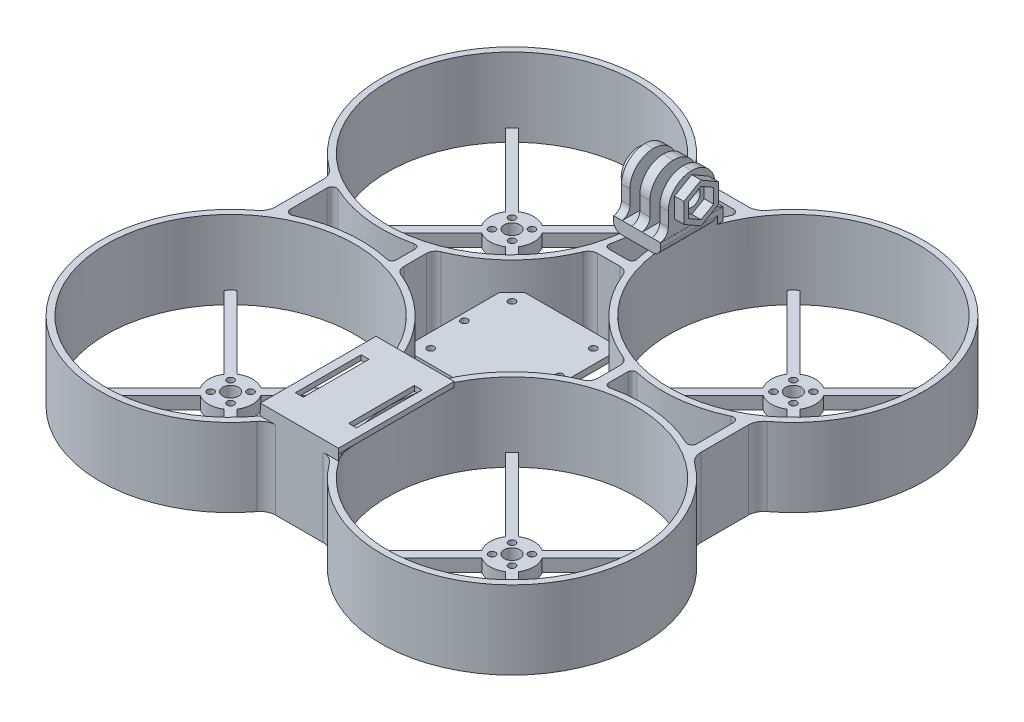
SolidWorks part; units mm, degrees
ref_plane "Front Plane" through (0, 0, 0) normal (0, 0, 1) x (1, 0, 0)
ref_plane "Top Plane" through (0, 0, 0) normal (0, 1, 0) x (1, 0, 0)
ref_plane "Right Plane" through (0, 0, 0) normal (1, 0, 0) x (0, 0, -1)
ref_axis "X Axis" through (-102.512, 0, 0) along (1, 0, 0)
ref_axis "Y Axis" through (0, 0, -107.1526) along (0, 0, 1)
ref_axis "Z Axis" through (0, 27.7441, 0) along (0, -1, 0)
ref_plane "Prop Guards Plane" through (0, 15, 0) normal (0, 1, 0) x (1, 0, 0)
ref_plane "Motor mount plane" through (0, 0, 0) normal (0, 1, 0) x (1, 0, 0)
sketch "Sketch1" plane through (0, 0, 0) normal (0, 1, 0) x (1, 0, 0)
  line L2 (-41.818, 48.182) -> (-48.182, 41.818) construction
  line L21 (-48.1744, 48.1895) -> (-41.8105, 41.8256) construction
  line L22 (48.182, 48.182) -> (41.818, 41.818) construction
  line L38 (-45, -45) -> (-45, 45) construction
  line L39 (-45, 45) -> (-40.5, 45) construction
  line L40 (45, -45) -> (45, 45) construction
  line L41 (-45, -45) -> (45, 45) construction
  line L42 (-45, 45) -> (45, -45) construction
  line L43 (-45, 45) -> (45, 45) construction
  line L44 (41.818, 48.182) -> (48.182, 41.818) construction
  line L45 (45, 45) -> (49.5, 45) construction
  line L46 (41.818, -41.818) -> (48.182, -48.182) construction
  line L47 (41.818, -48.182) -> (48.182, -41.818) construction
  line L48 (-45, -45) -> (45, -45) construction
  line L49 (-41.818, -41.818) -> (-48.182, -48.182) construction
  line L50 (-48.182, -41.818) -> (-41.818, -48.182) construction
  line L59 (0, 107.1526) -> (0, -108.5266) construction
  circle A2 centre (-45, 45) radius 4.5 construction
  circle A3 centre (-48.1744, 48.1895) radius 1.1
  circle A4 centre (-41.818, 48.182) radius 1.1
  circle A5 centre (-41.8105, 41.8256) radius 1.1
  circle A6 centre (-48.182, 41.818) radius 1.1
  circle A22 centre (-45, 45) radius 2.5
  circle A33 centre (-45, 45) radius 7
  circle A34 centre (-45, 45) radius 38.25 construction
  circle A35 centre (45, 45) radius 4.5 construction
  circle A36 centre (41.818, 48.182) radius 1.1
  circle A37 centre (48.182, 48.182) radius 1.1
  circle A38 centre (48.182, 41.818) radius 1.1
  circle A39 centre (41.818, 41.818) radius 1.1
  circle A40 centre (45, 45) radius 2.5
  circle A41 centre (45, 45) radius 7
  circle A42 centre (45, -45) radius 4.5 construction
  circle A43 centre (41.818, -48.182) radius 1.1
  circle A44 centre (41.818, -41.818) radius 1.1
  circle A45 centre (48.182, -41.818) radius 1.1
  circle A46 centre (48.182, -48.182) radius 1.1
  circle A47 centre (45, -45) radius 2.5
  circle A48 centre (45, -45) radius 7
  circle A49 centre (-45, -45) radius 4.5 construction
  circle A50 centre (-48.182, -41.818) radius 1.1
  circle A51 centre (-41.818, -41.818) radius 1.1
  circle A52 centre (-41.818, -48.182) radius 1.1
  circle A53 centre (-48.182, -48.182) radius 1.1
  circle A54 centre (-45, -45) radius 2.5
  circle A55 centre (-45, -45) radius 7
  circle A56 centre (45, 45) radius 38.25 construction
  circle A57 centre (45, -45) radius 38.25 construction
  circle A58 centre (-45, -45) radius 38.25 construction
  point P8 (45, 45)
  point P9 (0, 0)
  point P16 (-45, 45)
  point P26 (0, 0)
  point P29 (45, 45)
  point P39 (45, -45)
  point P46 (45, -45)
  point P50 (-45, 45)
  point P55 (-45, -45)
  point P64 (-45, -45)
  point P67 (0, 0)
  point P76 (0, 0)
  point P85 (0, 0)
  point P104 (0, 0)
  point P120 (0, 0)
  dimension "D3" = 14
  dimension "D4" = 9
  dimension "D7" = 76.5
  dimension "D5" = 2.2
  dimension "D6" = 5
  dimension "D8" = 9
  dimension "D10" = 5
  dimension "D12" = 14
  dimension "D13" = 9
  dimension "D15" = 5
  dimension "D17" = 9
  dimension "D19" = 5
  dimension "D20" = 14
  dimension "D11" = 90
extrude "Boss-Extrude3" add sketch "Sketch1" along normal blind 4
sketch "Sketch10" plane through (0, 0, 0) normal (0, 1, 0) x (1, 0, 0)
  line L0 (-72, 0) -> (0, 0) construction
  line L16 (0, 0) -> (0, 72) construction
  circle A0 centre (-45, 45) radius 39.75
  circle A1 centre (45, 45) radius 39.75
  circle A2 centre (45, -45) radius 39.75
  circle A3 centre (-45, -45) radius 39.75
  circle A4 centre (-45, 45) radius 41.75
  circle A5 centre (45, 45) radius 41.75
  circle A6 centre (45, -45) radius 41.75
  circle A7 centre (-45, -45) radius 41.75
  point P46 (0, 0)
  dimension "D1" = 79.5
  dimension "D3" = 72
  dimension "D2" = 2
extrude "Boss-Extrude8" add sketch "Sketch10" along normal blind 25 separate body contours A7 A3 | A6 A2 | A5 A1 | A4 A0 region at (-85.5691, 0, -45) region at (4.4309, 0, -45) region at (4.4309, 0, 45) region at (-85.5691, 0, 45)
sketch "Sketch21" plane through (0, 25, 0) normal (0, 1, 0) x (1, 0, 0)
  line L0 (-4.1275, 0) -> (4.1275, 0) construction
  line L1 (-34, 4.7252) -> (-34, -4.7252)
  line L6 (-31, 5.6673) -> (-31, -5.6673)
  line L7 (-34, 4.7252) -> (-31, 5.6673)
  line L8 (-31, -5.6673) -> (-34, -4.7252)
  line L33 (-68, 10.1566) -> (-68, -10.1566)
  line L45 (-65, 8.3522) -> (-65, -8.3522)
  line L46 (-68, 10.1566) -> (-65, 8.3522)
  line L47 (-68, -10.1566) -> (-65, -8.3522)
  line L65 (-10.1566, 68) -> (-8.3522, 65)
  line L66 (8.3522, 65) -> (-8.3522, 65)
  line L67 (10.1566, 68) -> (8.3522, 65)
  line L68 (10.1566, 68) -> (-10.1566, 68)
  line L69 (-5.6673, 31) -> (-4.7252, 34)
  line L70 (4.7252, 34) -> (-4.7252, 34)
  line L71 (4.7252, 34) -> (5.6673, 31)
  line L72 (5.6673, 31) -> (-5.6673, 31)
  line L73 (68, 10.1566) -> (65, 8.3522)
  line L74 (65, -8.3522) -> (65, 8.3522)
  line L75 (68, -10.1566) -> (65, -8.3522)
  line L76 (68, -10.1566) -> (68, 10.1566)
  line L77 (31, 5.6673) -> (34, 4.7252)
  line L78 (34, -4.7252) -> (34, 4.7252)
  line L79 (34, -4.7252) -> (31, -5.6673)
  line L80 (31, -5.6673) -> (31, 5.6673)
  line L81 (10.1566, -68) -> (8.3522, -65)
  line L82 (-8.3522, -65) -> (8.3522, -65)
  line L83 (-10.1566, -68) -> (-8.3522, -65)
  line L84 (-10.1566, -68) -> (10.1566, -68)
  line L85 (5.6673, -31) -> (4.7252, -34)
  line L86 (-4.7252, -34) -> (4.7252, -34)
  line L87 (-4.7252, -34) -> (-5.6673, -31)
  line L88 (-5.6673, -31) -> (5.6673, -31)
  circle A0 centre (-45, 45) radius 41.75 construction
  circle A1 centre (-45, -45) radius 41.75 construction
  point P0 (0, 0)
  point P38 (-0.0792, 0.1295)
  point P39 (0, 0)
  dimension "D1" = 3
  dimension "D2" = 3
  dimension "D3" = 68
  dimension "D4" = 34
  dimension "D5" = 4
extrude "Boss-Extrude15" add sketch "Sketch21" against normal up to surface (25 mm away) up to face at (-45, 0, -5.25)
sketch "Sketch22" plane through (0, 0, 0) normal (0, 1, 0) x (1, 0, 0)
  line L0 (0, 0) -> (-45, 45) construction
  line L2 (-39.1046, 41.2259) -> (-15.2428, 17.3641)
  line L3 (-39.1046, 41.2259) -> (-41.2259, 39.1046)
  line L4 (-41.2259, 39.1046) -> (-17.3641, 15.2428)
  line L5 (-15.2428, 17.3641) -> (-17.3641, 15.2428)
  line L6 (-39.1046, 41.2259) -> (-17.3641, 15.2428) construction
  line L7 (-41.2259, 39.1046) -> (-15.2428, 17.3641) construction
  line L8 (-48.7741, 39.1046) -> (-50.8954, 41.2259)
  line L9 (-48.7741, 39.1046) -> (-72.6359, 15.2428)
  line L10 (-72.6359, 15.2428) -> (-74.7572, 17.3641)
  line L11 (-50.8954, 41.2259) -> (-74.7572, 17.3641)
  line L12 (-50.8954, 48.7741) -> (-48.7741, 50.8954)
  line L13 (-50.8954, 48.7741) -> (-74.7572, 72.6359)
  line L14 (-74.7572, 72.6359) -> (-72.6359, 74.7572)
  line L15 (-48.7741, 50.8954) -> (-72.6359, 74.7572)
  line L16 (-41.2259, 50.8954) -> (-39.1046, 48.7741)
  line L17 (-41.2259, 50.8954) -> (-17.3641, 74.7572)
  line L18 (-17.3641, 74.7572) -> (-15.2428, 72.6359)
  line L19 (-39.1046, 48.7741) -> (-15.2428, 72.6359)
  line L20 (48.7741, 50.8954) -> (50.8954, 48.7741)
  line L21 (50.8954, 48.7741) -> (74.7572, 72.6359)
  line L22 (72.6359, 74.7572) -> (74.7572, 72.6359)
  line L23 (48.7741, 50.8954) -> (72.6359, 74.7572)
  line L24 (39.1046, 48.7741) -> (41.2259, 50.8954)
  line L25 (41.2259, 50.8954) -> (17.3641, 74.7572)
  line L26 (15.2428, 72.6359) -> (17.3641, 74.7572)
  line L27 (39.1046, 48.7741) -> (15.2428, 72.6359)
  line L28 (50.8954, 41.2259) -> (48.7741, 39.1046)
  line L29 (48.7741, 39.1046) -> (72.6359, 15.2428)
  line L30 (74.7572, 17.3641) -> (72.6359, 15.2428)
  line L31 (50.8954, 41.2259) -> (74.7572, 17.3641)
  line L32 (41.2259, 39.1046) -> (39.1046, 41.2259)
  line L33 (41.2259, 39.1046) -> (17.3641, 15.2428)
  line L34 (17.3641, 15.2428) -> (15.2428, 17.3641)
  line L35 (39.1046, 41.2259) -> (15.2428, 17.3641)
  line L36 (50.8954, -48.7741) -> (48.7741, -50.8954)
  line L37 (48.7741, -50.8954) -> (72.6359, -74.7572)
  line L38 (74.7572, -72.6359) -> (72.6359, -74.7572)
  line L39 (50.8954, -48.7741) -> (74.7572, -72.6359)
  line L40 (48.7741, -39.1046) -> (50.8954, -41.2259)
  line L41 (50.8954, -41.2259) -> (74.7572, -17.3641)
  line L42 (72.6359, -15.2428) -> (74.7572, -17.3641)
  line L43 (48.7741, -39.1046) -> (72.6359, -15.2428)
  line L44 (41.2259, -50.8954) -> (39.1046, -48.7741)
  line L45 (39.1046, -48.7741) -> (15.2428, -72.6359)
  line L46 (17.3641, -74.7572) -> (15.2428, -72.6359)
  line L47 (41.2259, -50.8954) -> (17.3641, -74.7572)
  line L48 (39.1046, -41.2259) -> (41.2259, -39.1046)
  line L49 (39.1046, -41.2259) -> (15.2428, -17.3641)
  line L50 (15.2428, -17.3641) -> (17.3641, -15.2428)
  line L51 (41.2259, -39.1046) -> (17.3641, -15.2428)
  line L52 (-48.7741, -50.8954) -> (-50.8954, -48.7741)
  line L53 (-50.8954, -48.7741) -> (-74.7572, -72.6359)
  line L54 (-72.6359, -74.7572) -> (-74.7572, -72.6359)
  line L55 (-48.7741, -50.8954) -> (-72.6359, -74.7572)
  line L56 (-39.1046, -48.7741) -> (-41.2259, -50.8954)
  line L57 (-41.2259, -50.8954) -> (-17.3641, -74.7572)
  line L58 (-15.2428, -72.6359) -> (-17.3641, -74.7572)
  line L59 (-39.1046, -48.7741) -> (-15.2428, -72.6359)
  line L60 (-50.8954, -41.2259) -> (-48.7741, -39.1046)
  line L61 (-48.7741, -39.1046) -> (-72.6359, -15.2428)
  line L62 (-74.7572, -17.3641) -> (-72.6359, -15.2428)
  line L63 (-50.8954, -41.2259) -> (-74.7572, -17.3641)
  line L64 (-41.2259, -39.1046) -> (-39.1046, -41.2259)
  line L65 (-41.2259, -39.1046) -> (-17.3641, -15.2428)
  line L66 (-17.3641, -15.2428) -> (-15.2428, -17.3641)
  line L67 (-39.1046, -41.2259) -> (-15.2428, -17.3641)
  circle A0 centre (-45, 45) radius 7 construction
  point P4 (-28.2343, 28.2343)
  point P9 (-27.94, 27.94)
  point P10 (-45, 45)
  point P30 (-45, 45)
  point P77 (-0.0652, 0)
  point P78 (0, 0)
  dimension "D1" = 3
  dimension "D2" = 4
  dimension "D3" = 4
extrude "Boss-Extrude16" add sketch "Sketch22" along normal blind 4
ref_plane "PCB Plane" through (0, 14, 0) normal (0, 1, 0) x (1, 0, 0)
sketch "Sketch13" plane through (0, 14, 0) normal (0, 1, 0) x (1, 0, 0)
  line L0 (-15.25, 0) -> (15.25, 0) construction
  line L1 (-13, -13) -> (13, -13) construction
  line L2 (-13, -13) -> (-13, 13) construction
  line L3 (-13, 13) -> (13, 13) construction
  line L4 (13, -13) -> (13, 13) construction
  line L5 (-13, -13) -> (13, 13) construction
  line L6 (-13, 13) -> (13, -13) construction
  line L7 (-14.5, -17.5) -> (14.5, -17.5)
  line L8 (-17.5, -14.5) -> (-17.5, 14.5)
  line L9 (-14.5, 17.5) -> (14.5, 17.5)
  line L10 (17.5, -14.5) -> (17.5, 14.5)
  line L11 (-17.5, -17.5) -> (17.5, 17.5) construction
  line L12 (-17.5, 17.5) -> (17.5, -17.5) construction
  circle A0 centre (-13, 13) radius 1.1
  circle A1 centre (13, 13) radius 1.1
  circle A2 centre (13, -13) radius 1.1
  circle A3 centre (-13, -13) radius 1.1
  circle A4 centre (-15.25, 0) radius 1.1
  circle A5 centre (15.25, 0) radius 1.1
  arc A6 (-14.5, -17.5) -> (-17.5, -14.5) centre (-14.5, -14.5) cw
  arc A7 (14.5, -17.5) -> (17.5, -14.5) centre (14.5, -14.5) ccw
  arc A8 (14.5, 17.5) -> (17.5, 14.5) centre (14.5, 14.5) cw
  arc A9 (-17.5, 14.5) -> (-14.5, 17.5) centre (-14.5, 14.5) cw
  point P0 (0, 0)
  point P10 (0, 0)
  point P17 (0, 0)
  dimension "D2" = 2.2
  dimension "D5" = 2.2
  dimension "D6" = 3
  dimension "D1" = 26
  dimension "D3" = 35
  dimension "D4" = 30.5
extrude "Boss-Extrude9" add sketch "Sketch13" along normal blind 2
sketch "Sketch14" plane through (0, 25, 0) normal (0, 1, 0) x (1, 0, 0)
  line L0 (0, 0) -> (0, 50) construction
  line L2 (-7.5, 40) -> (7.5, 40)
  line L3 (-7.5, 40) -> (-7.5, 60)
  line L4 (-7.5, 60) -> (7.5, 60)
  line L5 (7.5, 40) -> (7.5, 60)
  line L6 (-7.5, 40) -> (7.5, 60) construction
  line L7 (-7.5, 60) -> (7.5, 40) construction
  dimension "D1" = 20
  dimension "D2" = 15
  dimension "D3" = 50
extrude "Boss-Extrude10" add sketch "Sketch14" along normal blind 4
sketch "Sketch15" plane through (0, 29, 0) normal (0, 1, 0) x (1, 0, 0)
  line L0 (-7.5, 60) -> (7.5, 40) construction
  line L1 (-7.5, 40) -> (7.5, 60) construction
  line L2 (7.5, 40) -> (7.5, 60) construction
  line L3 (-7.5, 50) -> (7.5, 50) construction
  line L5 (0, -49.9102) -> (0, 49.9102) construction
  line L6 (-1.625, 42.5) -> (1.625, 42.5)
  line L7 (-1.625, 42.5) -> (-1.625, 57.5)
  line L8 (-1.625, 57.5) -> (1.625, 57.5)
  line L9 (1.625, 42.5) -> (1.625, 57.5)
  line L10 (-1.625, 42.5) -> (1.625, 57.5) construction
  line L11 (-1.625, 57.5) -> (1.625, 42.5) construction
  line L12 (-7.475, 42.5) -> (-4.775, 42.5)
  line L13 (-7.475, 42.5) -> (-7.475, 57.5)
  line L14 (-7.475, 57.5) -> (-4.775, 57.5)
  line L15 (-4.775, 42.5) -> (-4.775, 57.5)
  line L16 (-7.475, 42.5) -> (-4.775, 57.5) construction
  line L17 (-7.475, 57.5) -> (-4.775, 42.5) construction
  line L18 (7.475, 57.5) -> (4.775, 57.5)
  line L19 (4.775, 42.5) -> (4.775, 57.5)
  line L20 (7.475, 42.5) -> (4.775, 42.5)
  line L21 (7.475, 42.5) -> (7.475, 57.5)
  point P9 (0, 50)
  point P10 (0, 50)
  point P17 (0, 50)
  point P23 (-6.125, 50)
  dimension "D1" = 3.25
  dimension "D2" = 15
  dimension "D3" = 15
  dimension "D4" = 2.7
  dimension "D5" = 3.15
extrude "Boss-Extrude11" add sketch "Sketch15" along normal blind 15
fillet "Fillet10" radius 7.5 6 edges at (6.125, 44, -42.5) (6.125, 44, -57.5) (0, 44, -42.5) (0, 44, -57.5) (-6.125, 44, -42.5) (-6.125, 44, -57.5)
sketch "Sketch16" plane through (-7.475, 0, 0) normal (-1, 0, 0) x (0, 0, 1)
  circle A0 centre (-50, 36.5) radius 7.5 construction
  circle A3 centre (-50, 36.5) radius 2.7
  arc A4 (-50, 44) -> (-57.5, 36.5) centre (-50, 36.5) ccw construction
  dimension "D1" = 5.4
extrude "Cut-Extrude1" cut sketch "Sketch16" against normal blind 17 and the other way blind 12
sketch "Sketch17" plane through (-7.475, 0, 0) normal (-1, 0, 0) x (0, 0, 1)
  circle A0 centre (-50, 36.5) radius 5.5
  circle A1 centre (-50, 36.5) radius 2.7
  dimension "D1" = 11
extrude "Boss-Extrude12" add sketch "Sketch17" along normal blind 2.1
sketch "Sketch23" plane through (7.475, 0, 0) normal (1, 0, 0) x (0, 0, -1)
  line L0 (50, 42.8509) -> (44.5, 39.6754)
  line L1 (50, 41.1188) -> (46, 38.8094)
  line L2 (46, 38.8094) -> (46, 34.1906)
  line L3 (46, 34.1906) -> (50, 31.8812)
  line L4 (50, 31.8812) -> (54, 34.1906)
  line L5 (54, 34.1906) -> (54, 38.8094)
  line L6 (54, 38.8094) -> (50, 41.1188)
  line L7 (44.5, 39.6754) -> (44.5, 33.3246)
  line L8 (44.5, 33.3246) -> (50, 30.1491)
  line L9 (50, 30.1491) -> (55.5, 33.3246)
  line L10 (55.5, 33.3246) -> (55.5, 39.6754)
  line L11 (55.5, 39.6754) -> (50, 42.8509)
  circle A0 centre (50, 36.5) radius 4 construction
  dimension "D1" = 8
  dimension "D2" = 1.5
extrude "Boss-Extrude17" add sketch "Sketch23" along normal blind 3
fillet "Fillet12" radius 2.5 2 edges at (-7.5, 25, -49.0919) (7.5, 25, -49.0919)
fillet "Fillet11" radius 3 6 edges at (6.125, 29, -42.5) (0, 29, -42.5) (-6.125, 29, -42.5) (0, 29, -57.5) (6.125, 29, -57.5) (-6.125, 29, -57.5)
ref_plane "Battery plane" through (0, 27, 0) normal (0, 1, 0) x (1, 0, 0)
sketch "Sketch24" plane through (0, 27, 0) normal (0, 1, 0) x (1, 0, 0)
  line L0 (0, 0) -> (0, -49) construction
  line L1 (-8.5, -49) -> (8.5, -49) construction
  line L6 (5.6673, -31) -> (-5.6673, -31) construction
  line L7 (-12.5, -31) -> (12.5, -31)
  line L8 (-12.5, -31) -> (-12.5, -68)
  line L9 (-9.75, -59.5) -> (-7.25, -59.5)
  line L10 (-9.75, -59.5) -> (-9.75, -38.5)
  line L11 (-9.75, -38.5) -> (-7.25, -38.5)
  line L12 (-7.25, -59.5) -> (-7.25, -38.5)
  line L13 (-9.75, -59.5) -> (-7.25, -38.5) construction
  line L14 (-9.75, -38.5) -> (-7.25, -59.5) construction
  line L15 (7.25, -59.5) -> (9.75, -59.5)
  line L16 (7.25, -59.5) -> (7.25, -38.5)
  line L17 (7.25, -38.5) -> (9.75, -38.5)
  line L18 (9.75, -59.5) -> (9.75, -38.5)
  line L19 (7.25, -59.5) -> (9.75, -38.5) construction
  line L20 (7.25, -38.5) -> (9.75, -59.5) construction
  line L21 (-12.5, -68) -> (12.5, -68)
  line L22 (12.5, -31) -> (12.5, -68)
  line L23 (-12.5, -31) -> (12.5, -68) construction
  line L24 (-12.5, -68) -> (12.5, -31) construction
  line L25 (-10.1566, -68) -> (10.1566, -68) construction
  point P4 (0, -49.5)
  point P9 (-8.5, -49)
  point P14 (8.5, -49)
  point P19 (0, -49)
  dimension "D2" = 25
  dimension "D3" = 49
  dimension "D4" = 17
  dimension "D5" = 21
  dimension "D6" = 2.5
extrude "Boss-Extrude18" add sketch "Sketch24" along normal blind 1.6 separate body
sketch "Sketch25" plane through (0, 25, 0) normal (0, 1, 0) x (1, 0, 0)
  line L0 (-7.797, -31) -> (7.797, -31)
  line L1 (5.6673, -31) -> (-5.6673, -31) construction
  line L2 (-6.8023, -34) -> (6.8023, -34)
  line L3 (-4.7252, -34) -> (4.7252, -34) construction
  circle A0 centre (-45, -45) radius 39.75 construction
  circle A1 centre (45, -45) radius 39.75 construction
  arc A2 (-7.797, -31) -> (-6.8023, -34) centre (-45, -45) cw
  arc A3 (7.797, -31) -> (6.8023, -34) centre (45, -45) ccw
sketch "Sketch26" plane through (0, 27, 0) normal (0, -1, 0) x (1, 0, 0)
  line L0 (12.5, 68) -> (12.5, 31) construction
  line L1 (-12.5, 31) -> (12.5, 31)
  line L2 (-12.5, 31) -> (-12.5, 36.195)
  line L3 (-12.5, 36.195) -> (12.5, 36.195)
  line L4 (12.5, 31) -> (12.5, 36.195)
loft "Loft1" add profiles "Sketch25", "Sketch26"
sketch "Sketch27" plane through (0, 25, 0) normal (0, 1, 0) x (1, 0, 0)
  line L0 (-12.5799, -68) -> (12.5799, -68)
  line L2 (-10.1566, -68) -> (10.1566, -68) construction
  line L3 (10.648, -65) -> (-10.648, -65)
  line L4 (8.3522, -65) -> (-8.3522, -65) construction
  arc A0 (-7.797, -31) -> (-6.8023, -34) centre (-45, -45) ccw construction
  arc A1 (6.8023, -34) -> (7.797, -31) centre (45, -45) ccw construction
  arc A2 (-10.648, -65) -> (-12.5799, -68) centre (-45, -45) cw
  arc A3 (10.648, -65) -> (12.5799, -68) centre (45, -45) ccw
  point P17 (0, 0)
sketch "Sketch28" plane through (0, 27, 0) normal (0, -1, 0) x (1, 0, 0)
  line L0 (-12.5, 36.195) -> (-12.5, 68) construction
  line L1 (12.5, 68) -> (-12.5, 68)
  line L2 (12.5, 68) -> (12.5, 63.3482)
  line L3 (12.5, 63.3482) -> (-12.5, 63.3482)
  line L4 (-12.5, 68) -> (-12.5, 63.3482)
loft "Loft2" add profiles "Sketch27", "Sketch28"
fillet "Fillet14" radius 5 8 edges at (-68, 12.5, 10.1566) (-68, 12.5, -10.1566) (10.1566, 12.5, -68) (-10.1566, 12.5, -68) (68, 12.5, 10.1566) (68, 12.5, -10.1566)
fillet "Fillet15" radius 1.5 8 edges at (65, 12.5, -8.3522) (65, 12.5, 8.3522) (8.3522, 12.5, -65) (-8.3522, 12.5, -65) (-65, 12.5, -8.3522) (-65, 12.5, 8.3522)
fillet "Fillet16" radius 3 8 edges at (-31, 12.5, -5.6673) (-31, 12.5, 5.6673) (-5.6673, 12.5, -31) (5.6673, 12.5, -31) (31, 12.5, -5.6673) (31, 12.5, 5.6673)
fillet "Fillet17" radius 1.3 8 edges at (34, 12.5, -4.7252) (34, 12.5, 4.7252) (4.7252, 12.5, -34) (-4.7252, 12.5, -34) (-34, 12.5, -4.7252) (-34, 12.5, 4.7252)
equation "\"Prop Dia\"= 76.2mm"
equation "\"ground_clearance\"= 15mm"
equation "\"D1@Prop Guards Plane\"=\"ground_clearance\""
